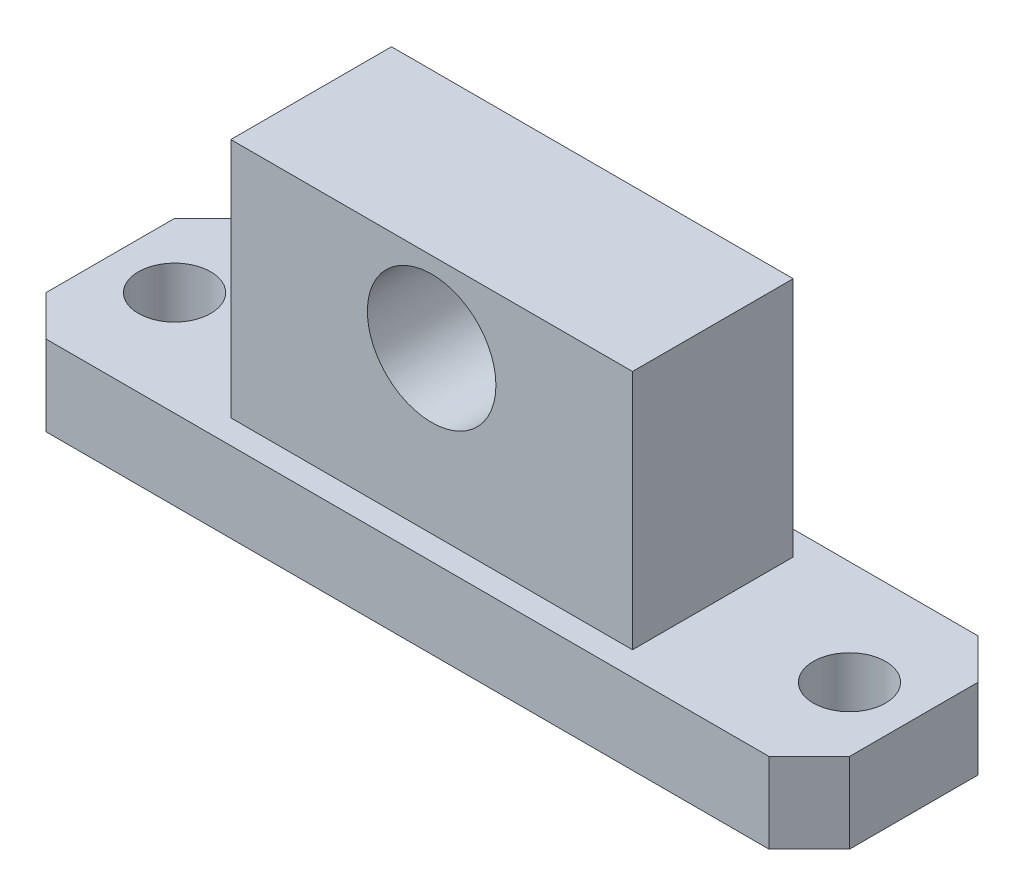
SolidWorks part; units mm, degrees
material "6061 Alloy"
ref_plane "Front Plane" through (0, 0, 0) normal (0, 0, 1) x (1, 0, 0)
ref_plane "Top Plane" through (0, 0, 0) normal (0, 1, 0) x (1, 0, 0)
ref_plane "Right Plane" through (0, 0, 0) normal (1, 0, 0) x (0, 0, -1)
sketch "Sketch1" plane through (0, 0, 0) normal (0, 1, 0) x (1, 0, 0)
  line L1 (-25, -6.5) -> (25, -6.5)
  line L2 (-25, -6.5) -> (-25, 6.5)
  line L3 (-25, 6.5) -> (25, 6.5)
  line L4 (25, -6.5) -> (25, 6.5)
  line L5 (-25, -6.5) -> (25, 6.5) construction
  line L6 (-25, 6.5) -> (25, -6.5) construction
  point P0 (0, 0)
  dimension "D1" = 13
  dimension "D2" = 50
extrude "Boss-Extrude1" add sketch "Sketch1" along normal blind 5
sketch "Sketch2" plane through (0, 5, 0) normal (0, 1, 0) x (1, 0, 0)
  line L1 (-25, 6.5) -> (-25, -6.5) construction
  circle A0 centre (-21, 0) radius 2.25
  circle A1 centre (21, 0) radius 2.25
  dimension "D1" = 4.5
  dimension "D2" = 4.5
  dimension "D3" = 42
  dimension "D4" = 4
extrude "Cut-Extrude1" cut sketch "Sketch2" against normal blind 5
sketch "Sketch3" plane through (0, 5, 0) normal (0, 1, 0) x (1, 0, 0)
  line L1 (-12.5, -5) -> (12.5, -5)
  line L2 (-12.5, -5) -> (-12.5, 5)
  line L3 (-12.5, 5) -> (12.5, 5)
  line L4 (12.5, -5) -> (12.5, 5)
  line L5 (-12.5, -5) -> (12.5, 5) construction
  line L6 (-12.5, 5) -> (12.5, -5) construction
  point P0 (0, 0)
  dimension "D1" = 10
  dimension "D2" = 25
extrude "Boss-Extrude2" add sketch "Sketch3" along normal blind 15
sketch "Sketch4" plane through (0, 0, 5) normal (0, 0, 1) x (1, 0, 0)
  line L1 (-25, 0) -> (25, 0) construction
  circle A0 centre (0, 15) radius 4
  dimension "D1" = 8
  dimension "D2" = 15
extrude "Cut-Extrude2" cut sketch "Sketch4" against normal blind 15
chamfer "Chamfer1" distance 2.5 angle 45 4 edges at (25, 2.5, 6.5) (25, 2.5, -6.5) (-25, 2.5, 6.5) (-25, 2.5, -6.5)
